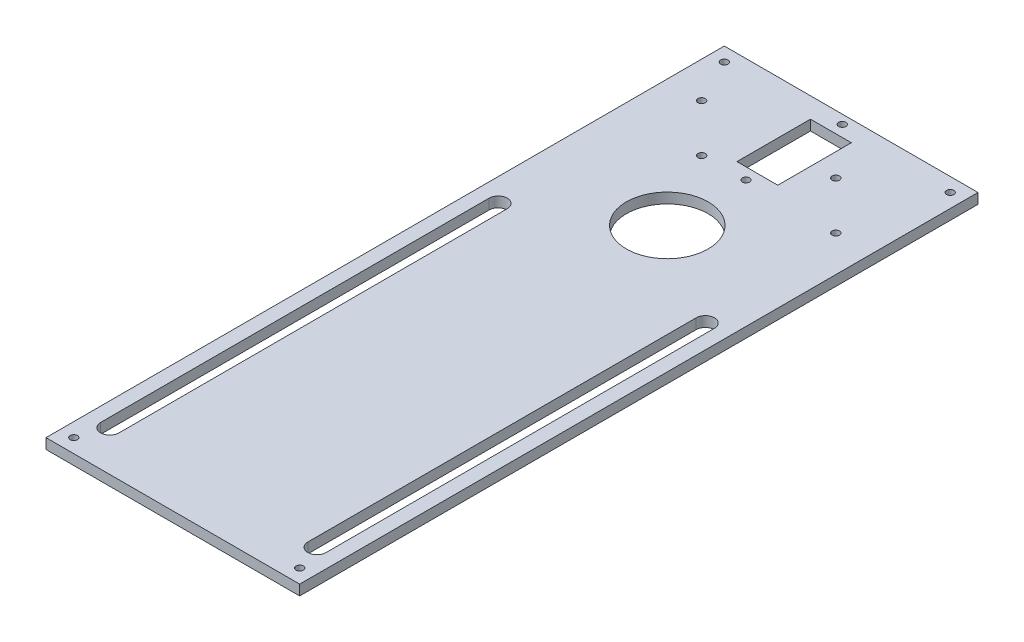
SolidWorks part; units mm, degrees
material "Brass"
ref_plane "Front Plane" through (0, 0, 0) normal (0, 0, 1) x (1, 0, 0)
ref_plane "Top Plane" through (0, 0, 0) normal (0, 1, 0) x (1, 0, 0)
ref_plane "Right Plane" through (0, 0, 0) normal (1, 0, 0) x (0, 0, -1)
sketch "Sketch2" plane through (0, 0, 0) normal (0, 0, 1) x (1, 0, 0)
  line L0 (-44.45, 0) -> (-44.45, -3.2004)
  line L1 (0, 0) -> (0, -3.2004) construction
  line L2 (-44.45, -3.2004) -> (34.3945, -3.2004)
  line L3 (34.3945, 0) -> (34.3945, -3.2004)
  line L4 (-44.45, 0) -> (34.3945, 0)
  dimension "D1" = 78.8445
  dimension "D2" = 3.2004
extrude "Boss-Extrude1" add sketch "Sketch2" along normal blind 210.82 contours L4 L3 L2 L0
sketch "Sketch3" plane through (0, -3.2004, 0) normal (0, -1, 0) x (1, 0, 0)
  line L0 (-44.45, 57.15) -> (34.3945, 57.15) construction
  line L1 (30.0765, 210.82) -> (30.0765, 206.502) construction
  line L2 (30.0765, 206.502) -> (34.3945, 206.502) construction
  line L3 (-44.45, 210.82) -> (34.3945, 210.82) construction
  line L4 (-5.0278, 57.15) -> (-5.0278, 0) construction
  line L5 (-44.45, 0) -> (34.3945, 0) construction
  line L6 (-40.0535, 77.5174) -> (-34.3859, 77.5174) construction
  line L7 (-40.0535, 77.5174) -> (-40.0535, 198.224)
  line L8 (-40.0535, 198.224) -> (-34.3859, 198.224) construction
  line L9 (-34.3859, 77.5174) -> (-34.3859, 198.224)
  line L10 (-37.2197, 210.82) -> (-37.2197, 201.0579) construction
  line L11 (-40.0535, 137.8707) -> (-44.45, 137.8707) construction
  line L12 (24.3303, 77.5174) -> (29.998, 77.5174) construction
  line L13 (24.3303, 77.5174) -> (24.3303, 198.224)
  line L14 (24.3303, 198.224) -> (29.998, 198.224) construction
  line L15 (29.998, 77.5174) -> (29.998, 198.224)
  line L16 (27.1642, 210.82) -> (27.1642, 201.0579) construction
  line L17 (34.3945, 137.8707) -> (29.998, 137.8707) construction
  line L18 (34.3945, 210.82) -> (34.3945, 0) construction
  line L19 (-44.45, 4.318) -> (-40.132, 4.318) construction
  line L20 (34.3945, 210.82) -> (34.3945, 0) construction
  line L21 (-44.45, 210.82) -> (-44.45, 0) construction
  line L22 (-44.45, 210.82) -> (-44.45, 0) construction
  line L23 (-40.132, 210.82) -> (-40.132, 206.502) construction
  line L24 (-44.45, 206.502) -> (-40.132, 206.502) construction
  line L25 (-44.45, 210.82) -> (34.3945, 210.82) construction
  line L26 (-40.132, 4.318) -> (-40.132, 0) construction
  line L27 (-44.45, 0) -> (34.3945, 0) construction
  line L28 (34.3945, 4.318) -> (30.0765, 4.318) construction
  line L29 (30.0765, 0) -> (30.0765, 4.318) construction
  line L30 (-11.3778, 29.1559) -> (-11.3778, 6.2959)
  line L31 (1.3222, 29.1559) -> (1.3222, 6.2959)
  line L32 (-11.3778, 6.2959) -> (1.3222, 6.2959)
  line L33 (-11.3778, 29.1559) -> (1.3222, 29.1559)
  line L34 (-18.4797, 33.02) -> (-33.2664, 18.2334) construction
  line L35 (23.2109, 33.02) -> (8.4242, 18.2334) construction
  line L36 (-44.45, 0) -> (34.3945, 0) construction
  line L37 (-33.2664, 18.2334) -> (-44.45, 18.2334) construction
  line L39 (34.3945, 33.02) -> (23.2109, 33.02) construction
  line L40 (23.2109, 33.02) -> (23.2109, 0) construction
  line L41 (23.2109, 33.02) -> (-18.4797, 33.02) construction
  circle A0 centre (-5.0278, 57.15) radius 12.7
  arc A1 (-40.0535, 198.224) -> (-34.3859, 198.224) centre (-37.2197, 198.224) cw
  arc A2 (-34.3859, 77.5174) -> (-40.0535, 77.5174) centre (-37.2197, 77.5174) cw
  arc A3 (24.3303, 198.224) -> (29.998, 198.224) centre (27.1642, 198.224) cw
  arc A4 (29.998, 77.5174) -> (24.3303, 77.5174) centre (27.1642, 77.5174) cw
  circle A5 centre (-40.132, 206.502) radius 1.1303
  circle A6 centre (30.0765, 206.502) radius 1.1303
  circle A7 centre (-40.132, 4.318) radius 1.1303
  circle A8 centre (30.0765, 4.318) radius 1.1303
  circle A9 centre (-5.0278, 32.6865) radius 1.1303
  circle A10 centre (-5.0278, 2.7653) radius 1.1303
  circle A11 centre (23.2109, 33.02) radius 1.143
  circle A12 centre (8.4242, 18.2334) radius 1.143
  circle A13 centre (-18.4797, 33.02) radius 1.143
  circle A14 centre (-33.2664, 18.2334) radius 1.143
  point P53 (-5.0278, 29.1559)
  point P58 (-5.0278, 29.1559)
  point P67 (-5.0278, 6.2959)
  dimension "D1" = 25.4
  dimension "D11" = 2.2606
  dimension "D15" = 2.2606
  dimension "D16" = 2.7653
  dimension "D18" = 3.5306
  dimension "D19" = 45
  dimension "D25" = 2.286
  dimension "D2" = 57.15
  dimension "D3" = 120.7066
  dimension "D4" = 5.6676
  dimension "D5" = 9.7621
  dimension "D6" = 4.3965
  dimension "D7" = 120.7066
  dimension "D8" = 5.6676
  dimension "D9" = 9.7621
  dimension "D10" = 4.3965
  dimension "D12" = 4.318
  dimension "D13" = 22.86
  dimension "D14" = 12.7
  dimension "D17" = 3.5306
  dimension "D20" = 11.1836
  dimension "D23" = 33.02
  dimension "D26" = 11.1836
  dimension "D27" = 20.9115
extrude "Cut-Extrude1" cut sketch "Sketch3" against normal through all
sketch "Sketch4" plane through (0, 0, 210.82) normal (0, 0, 1) x (1, 0, 0)
  line L0 (-5.0278, 0) -> (-5.0278, -3.2004) construction
  line L1 (-44.45, 0) -> (34.3945, 0) construction
  line L2 (-44.45, -3.2004) -> (34.3945, -3.2004) construction
sketch "Sketch6" plane through (34.3945, 0, 0) normal (1, 0, 0) x (0, 0, -1)
  line L0 (-105.41, 0) -> (-105.41, -3.2004) construction
  line L3 (-210.82, -3.2004) -> (0, -3.2004) construction
  line L4 (-210.82, 0) -> (0, 0) construction
